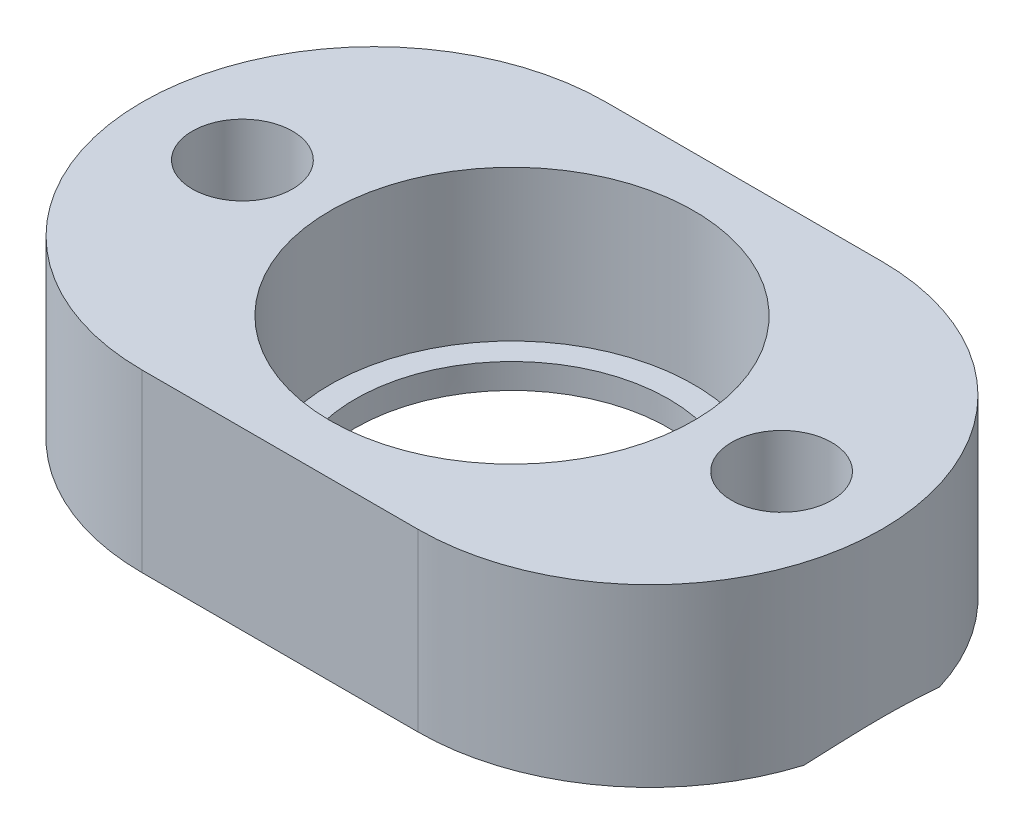
SolidWorks part; units mm, degrees
ref_plane "Front Plane" through (0, 0, 0) normal (0, 0, 1) x (1, 0, 0)
ref_plane "Top Plane" through (0, 0, 0) normal (0, 1, 0) x (1, 0, 0)
ref_plane "Right Plane" through (0, 0, 0) normal (1, 0, 0) x (0, 0, -1)
sketch "Sketch1" plane through (0, 0, 0) normal (0, 1, 0) x (1, 0, 0)
  line L0 (-5.5, 0) -> (5.5, 0) construction
  line L1 (-5.5, 9.25) -> (5.5, 9.25)
  line L2 (-5.5, -9.25) -> (5.5, -9.25)
  line L3 (-10.75, 0) -> (10.75, 0) construction
  circle A0 centre (0, 0) radius 7.25
  circle A1 centre (0, 0) radius 6.25
  circle A3 centre (-10.75, 0) radius 2
  arc A4 (-5.5, 9.25) -> (-5.5, -9.25) centre (-5.5, 0) ccw
  arc A5 (5.5, -9.25) -> (5.5, 9.25) centre (5.5, 0) ccw
  circle A6 centre (10.75, 0) radius 2
  point P9 (0, 0)
  point P14 (0, 7.25)
  point P15 (14.75, 0)
  point P16 (12.75, 0)
  dimension "D1" = 14.5
  dimension "D2" = 1
  dimension "D5" = 4
  dimension "D3" = 2
  dimension "D4" = 21.5
  dimension "D6" = 2
extrude "Boss-Extrude1" add sketch "Sketch1" along normal blind 6 contours L2 A5 L1 A4 A6 A0 A3 region at (0, 0, -8.9018)
extrude "Boss-Extrude2" add sketch "Sketch1<3>" against normal blind 1 contours L2 A5 L1 A4 A6 A0 A3 | A0 A1 region at (0, 0, -8.9018) region at (-7.0449, 0, 0)
sketch "Sketch1<3>" plane through (0, 0, 0) normal (0, 1, 0) x (1, 0, 0) same geometry as "Sketch1"
chamfer "Chamfer1" distance 2.5 angle 45 2 edges at (10.75, -1, 2) (-10.75, -1, 2)
